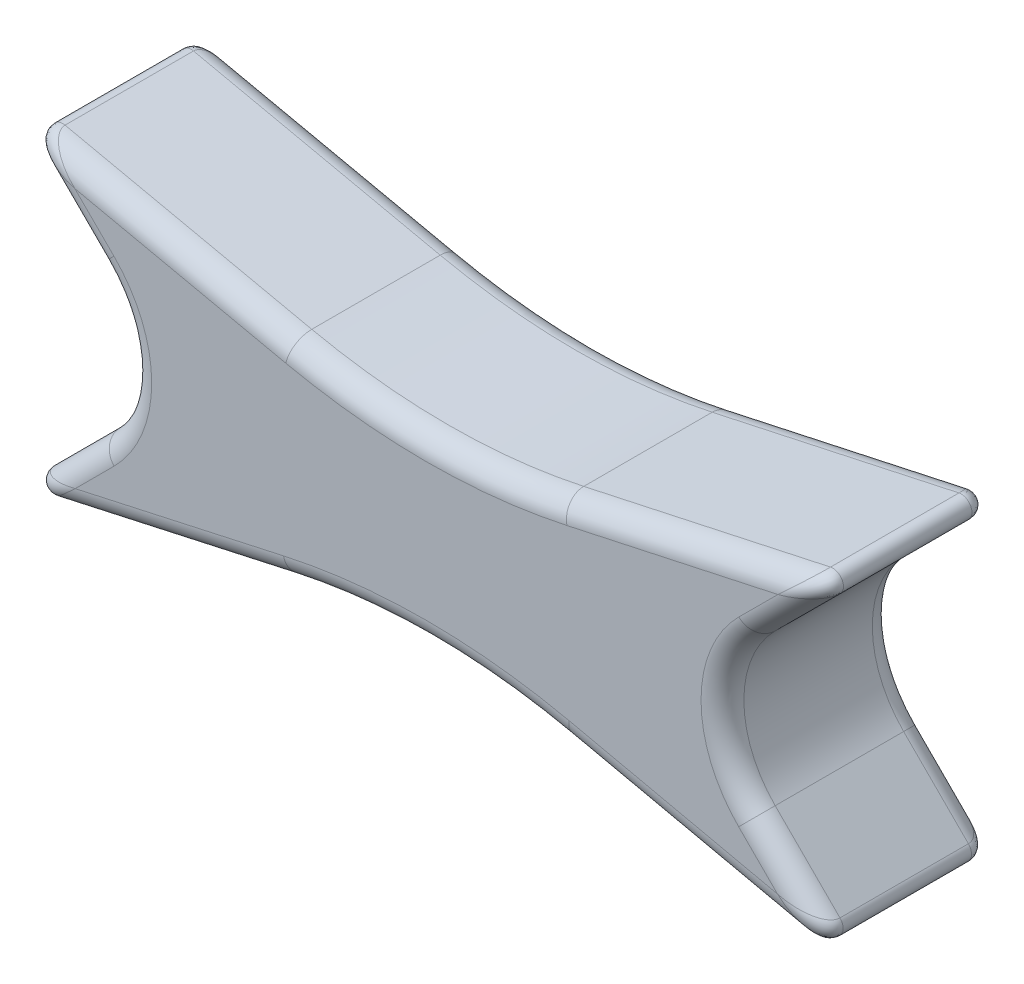
SolidWorks part; units mm, degrees
ref_plane "Front Plane" through (0, 0, 0) normal (0, 0, 1) x (1, 0, 0)
ref_plane "Top Plane" through (0, 0, 0) normal (0, 1, 0) x (1, 0, 0)
ref_plane "Right Plane" through (0, 0, 0) normal (1, 0, 0) x (0, 0, -1)
sketch "Sketch1" plane through (0, 0, 0) normal (0, 0, 1) x (1, 0, 0)
  line L4 (0, -55) -> (0, 55) construction
  line L10 (-63.5336, 49.8777) -> (-178.7878, 74.8526)
  line L11 (-183.3755, 66.4238) -> (-153.0199, 36.1828)
  line L12 (-152.9489, -34.5906) -> (-183.2069, -64.8555)
  line L13 (-178.5942, -73.2734) -> (-64.604, -48.1362)
  line L14 (183.3755, 66.4238) -> (153.0199, 36.1828)
  line L15 (178.5942, -73.2734) -> (64.604, -48.1362)
  line L16 (152.9489, -34.5906) -> (183.2069, -64.8555)
  line L17 (63.5336, 49.8777) -> (178.7878, 74.8526)
  arc A0 (64.604, -48.1362) -> (-64.604, -48.1362) centre (0, -341.0975) ccw
  arc A1 (63.5336, 49.8777) -> (-63.5336, 49.8777) centre (0, 343.073) cw
  arc A2 (153.0199, 36.1828) -> (152.9489, -34.5906) centre (188.3083, 0.7607) ccw
  arc A3 (-153.0199, 36.1828) -> (-152.9489, -34.5906) centre (-188.3083, 0.7607) cw
  arc A4 (-178.7878, 74.8526) -> (-183.3755, 66.4238) centre (-179.8467, 69.966) ccw
  arc A5 (-183.2069, -64.8555) -> (-178.5942, -73.2734) centre (-179.6709, -68.3907) ccw
  arc A6 (178.5942, -73.2734) -> (183.2069, -64.8555) centre (179.6709, -68.3907) ccw
  arc A7 (183.3755, 66.4238) -> (178.7878, 74.8526) centre (179.8467, 69.966) ccw
  point P2 (0, 0)
  point P6 (-198.3188, 115.3574)
  point P8 (-198.3188, -55.7002)
  point P9 (-129.0208, 22.2478)
  point P10 (-198.3188, 90.4522)
  point P11 (-124.1491, 0)
  point P12 (-198.3188, 79.0848)
  point P13 (-198.3188, -77.6231)
  point P20 (0, -33.8897)
  point P23 (0, 36.1103)
  point P26 (117.5347, 0.8317)
  point P30 (-117.5347, 0.8317)
  point P33 (-195.4635, 78.4661)
  point P36 (-195.3075, -76.959)
  point P39 (195.3075, -76.959)
  point P42 (195.4635, 78.4661)
  dimension "D1" = 70
  dimension "D2" = 200
  dimension "D6" = 300
  dimension "D7" = 50
  dimension "D8" = 5
  dimension "D3" = 200
  dimension "D4" = 110
  dimension "D5" = 110
extrude "Boss-Extrude1" add sketch "Sketch1" along normal blind 80
sketch "Sketch3" plane through (0, 0, 0) normal (0, 0, 1) x (1, 0, 0)
  circle A0 centre (0, 0) radius 33.1262
extrude "Cut-Extrude1" cut sketch "Sketch3" along normal blind 70
fillet "Fillet1" radius 10 32 edges at (121.1607, 62.3651, 0) (184.2383, 72.3563, 0) (168.1977, 51.3033, 0) (138.3083, 0.8108, 0) (168.0779, -49.7231, 0) (184.0558, -70.7934, 0) (121.5991, -60.7048, 0) (0, -41.0975, 0) (-121.5991, -60.7048, 0) (-184.0558, -70.7934, 0) (-168.0779, -49.7231, 0) (-138.3083, 0.8108, 0) (-168.1977, 51.3033, 0) (-184.2383, 72.3563, 0) (-121.1607, 62.3651, 0) (121.1607, 62.3651, 80) (184.2383, 72.3563, 80) (168.1977, 51.3033, 80) (138.3083, 0.8108, 80) (168.0779, -49.7231, 80) (184.0558, -70.7934, 80) (121.5991, -60.7048, 80) (0, -41.0975, 80) (-121.5991, -60.7048, 80) (-184.0558, -70.7934, 80) (-168.0779, -49.7231, 80) (-138.3083, 0.8108, 80) (-168.1977, 51.3033, 80) (-184.2383, 72.3563, 80) (-121.1607, 62.3651, 80) (0, 43.073, 0) (0, 43.073, 80)
